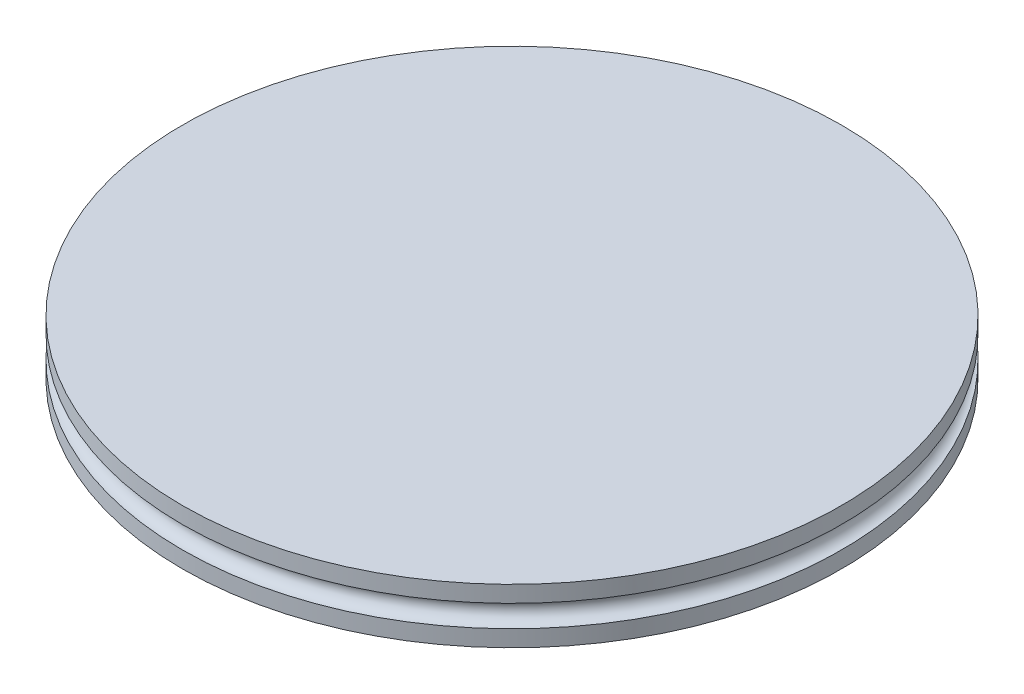
SolidWorks part; units mm, degrees
ref_plane "Front Plane" through (0, 0, 0) normal (0, 0, 1) x (1, 0, 0)
ref_plane "Top Plane" through (0, 0, 0) normal (0, 1, 0) x (1, 0, 0)
ref_plane "Right Plane" through (0, 0, 0) normal (1, 0, 0) x (0, 0, -1)
sketch "Sketch1" plane through (0, 0, 0) normal (0, 1, 0) x (1, 0, 0)
  circle A0 centre (0, 0) radius 7.62
extrude "Boss-Extrude1" add sketch "Sketch1" along normal blind 1.27
sketch "Sketch3" plane through (0, 0, 0) normal (0, 0, 1) x (1, 0, 0)
  line L0 (7.62, 1.27) -> (-7.62, 1.27) construction
  line L1 (-7.62, 1.27) -> (-7.62, 0) construction
  circle A0 centre (-7.112, 0.635) radius 0.254
  point P2 (-6.6935, 1.4702)
  point P5 (-7.1158, 1.5875)
  dimension "D1" = 0.635
  dimension "D2" = 0.508
extrude "Cut-Extrude1" cut sketch "Sketch3" against normal mid plane 50.8
sketch "Sketch4" plane through (0, 0, 0) normal (0, 0, 1) x (1, 0, 0)
  line L0 (7.62, 0) -> (7.62, 1.27) construction
  circle A0 centre (7.62, 0.635) radius 0.254
sketch "Sketch5" plane through (0, 0, 0) normal (0, 1, 0) x (1, 0, 0)
  line L0 (0, 0) -> (-7.5548, -0.9946) construction
  line L1 (0, 0) -> (-7.5548, 0.9946) construction
  line L2 (0, 0) -> (-7.62, 0) construction
  arc A0 (-7.5548, -0.9946) -> (-7.5548, 0.9946) centre (0, 0) ccw
  dimension "D1" = 15
  dimension "D2" = 7.5
ref_plane "Plane1" through (0, 0, -7.62) normal (0, 0, 1) x (1, 0, 0)
ref_plane "Plane2" through (0, 0, 7.62) normal (0, 0, 1) x (1, 0, 0)
sketch "Sketch6" plane through (0, 0, -7.62) normal (0, 0, 1) x (1, 0, 0)
  line L0 (-7.62, 1.27) -> (-7.62, 0) construction
  line L1 (-7.112, 0.889) -> (-7.62, 0.889)
  line L2 (-7.112, 0.889) -> (-7.112, 0.381)
  line L3 (-7.112, 0.381) -> (-7.62, 0.381)
  line L4 (-7.62, 0.889) -> (-7.62, 0.381)
  circle A0 centre (-7.112, 0.635) radius 0.254 construction
  point P8 (-7.112, 0.4974)
  point P9 (0, 0)
  dimension "D1" = 0.508
extrude "Cut-Extrude2" cut sketch "Sketch6" along normal blind 7.366
sketch "Sketch7" plane through (0, 0, 7.62) normal (0, 0, 1) x (1, 0, 0)
  line L0 (-7.62, 1.27) -> (-7.62, 0) construction
  line L1 (-7.112, 0.889) -> (-7.62, 0.889)
  line L2 (-7.112, 0.889) -> (-7.112, 0.381)
  line L3 (-7.112, 0.381) -> (-7.62, 0.381)
  line L4 (-7.62, 0.889) -> (-7.62, 0.381)
  circle A0 centre (-7.112, 0.635) radius 0.254 construction
extrude "Cut-Extrude3" cut sketch "Sketch7" against normal blind 7.366
sweep "Cut-Sweep1" cut profiles "Sketch4" path "Sketch5"
